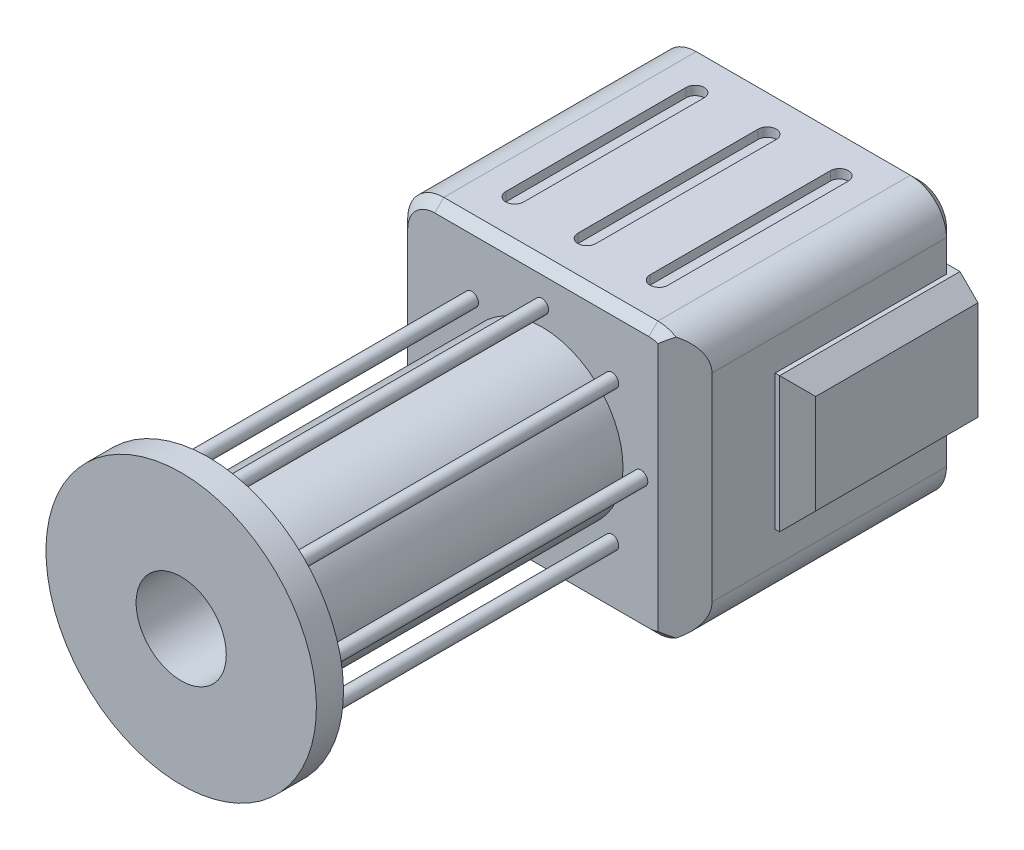
SolidWorks part; units mm, degrees
material "6061 Alloy"
ref_plane "Front Plane" through (0, 0, 0) normal (0, 0, 1) x (1, 0, 0)
ref_plane "Top Plane" through (0, 0, 0) normal (0, 1, 0) x (1, 0, 0)
ref_plane "Right Plane" through (0, 0, 0) normal (1, 0, 0) x (0, 0, -1)
sketch "Sketch2" plane through (0, 0, 0) normal (0, 0, 1) x (1, 0, 0)
  line L1 (-15.8755, 15) -> (15.8755, 15)
  line L2 (-15.8755, 15) -> (-15.8755, -15)
  line L3 (-15.8755, -15) -> (15.8755, -15)
  line L4 (15.8755, 15) -> (15.8755, -15)
  line L5 (-15.8755, 15) -> (15.8755, -15) construction
  line L6 (-15.8755, -15) -> (15.8755, 15) construction
  point P0 (0, 0)
  dimension "D1" = 30
extrude "Boss-Extrude1" add sketch "Sketch2" along normal mid plane 30
sketch "Sketch3" plane through (0, 0, 0) normal (1, 0, 0) x (0, 0, -1)
  line L0 (-15, 0) -> (-55, 0) construction
  line L1 (-15, -15) -> (-15, 15) construction
  line L2 (-55, 0) -> (-55, 15)
  line L3 (-55, 15) -> (-52, 15)
  line L4 (-52, 15) -> (-52, 9)
  line L5 (-52, 9) -> (-15, 9)
  line L6 (-15, 9) -> (-15, 0)
  line L7 (-15, 0) -> (-55, 0)
  dimension "D1" = 40
  dimension "D2" = 18
  dimension "D3" = 30
  dimension "D4" = 3
revolve "Revolve1" add sketch "Sketch3" angle 360 about L0
fillet "Fillet1" radius 4 4 edges at (-15.8755, -15, 0) (15.8755, -15, 0) (-15.8755, 15, 0) (15.8755, 15, 0)
chamfer "Chamfer1" distance 3 angle 45 1 edges at (15.8755, 0, 15) tangent propagation no
chamfer "Chamfer2" distance 1 angle 45 15 edges at (0, -15, -15) (14.7039, -13.8284, -15) (-14.7039, -13.8284, -15) (15.8755, 0, -15) (-15.8755, 0, -15) (14.7039, 13.8284, -15) (-14.7039, 13.8284, -15) (0, 15, -15) (12.3795, -14.9681, 15) (0, -15, 15) (-14.7039, -13.8284, 15) (-15.8755, 0, 15) (12.3795, 14.9681, 15) (-14.7039, 13.8284, 15) (0, 15, 15)
sketch "Sketch4" plane through (0, 0, -15) normal (0, 0, -1) x (-1, 0, 0)
  circle A0 centre (0, 0) radius 10
  dimension "D1" = 20
extrude "Boss-Extrude2" add sketch "Sketch4" along normal blind 5
fillet "Fillet2" radius 5 1 edges at (-10, 0, -20)
sketch "Sketch5" plane through (0, 0, -15) normal (0, 0, -1) x (-1, 0, 0)
  line L0 (-15.8755, -11) -> (-15.8755, 11) construction
  line L5 (-18.3755, 7.5) -> (-13.3755, 7.5)
  line L6 (-18.3755, 7.5) -> (-18.3755, -7.5)
  line L7 (-18.3755, -7.5) -> (-13.3755, -7.5)
  line L8 (-13.3755, 7.5) -> (-13.3755, -7.5)
  line L9 (-18.3755, 7.5) -> (-13.3755, -7.5) construction
  line L10 (-18.3755, -7.5) -> (-13.3755, 7.5) construction
  point P0 (-15.8755, 0)
  dimension "D1" = 15
  dimension "D2" = 5
extrude "Boss-Extrude3" add sketch "Sketch5" against normal blind 20
chamfer "Chamfer3" distance 2 angle 45 3 edges at (18.3755, -7.5, -5) (18.3755, 7.5, -5) (18.3755, 0, 5) tangent propagation no
sketch "Sketch6" plane through (0, 0, 55) normal (0, 0, 1) x (1, 0, 0)
  circle A0 centre (0, 0) radius 5
extrude "Cut-Extrude1" cut sketch "Sketch6" against normal blind 10
sketch "Sketch7" plane through (0, 0, 55) normal (0, 0, 1) x (1, 0, 0)
  line L0 (0, 0) -> (0, 11) construction
  circle A0 centre (0, 11) radius 0.75
  dimension "D1" = 1.5
  dimension "D2" = 11
extrude "Boss-Extrude4" add sketch "Sketch7" against normal up to surface (40 mm away) up to face at (0, 9, 15)
pattern_circular "CirPattern2" count 8 over 360 about axis through (0, 0, 55) along (0, 0, -1) of "Boss-Extrude4"
sketch "Sketch8" plane through (-15.8755, 0, 0) normal (-1, 0, 0) x (0, 0, 1)
  circle A0 centre (0, 0) radius 5
extrude "Cut-Extrude2" cut sketch "Sketch8" against normal blind 10
sketch "Sketch9" plane through (0, 15, 0) normal (0, 1, 0) x (1, 0, 0)
  line L0 (0, 10) -> (0, -10) construction
  line L1 (1, 10) -> (1, -10)
  line L2 (-1, 10) -> (-1, -10)
  arc A0 (1, 10) -> (-1, 10) centre (0, 10) ccw
  arc A1 (-1, -10) -> (1, -10) centre (0, -10) ccw
  point P2 (0, 0)
  dimension "D1" = 2
  dimension "D2" = 20
extrude "Cut-Extrude3" cut sketch "Sketch9" against normal blind 1
pattern_linear "LPattern3" count 2 spacing 8 along (-1, 0, 0) count 2 spacing 8 along (1, 0, 0) of "Cut-Extrude3"
